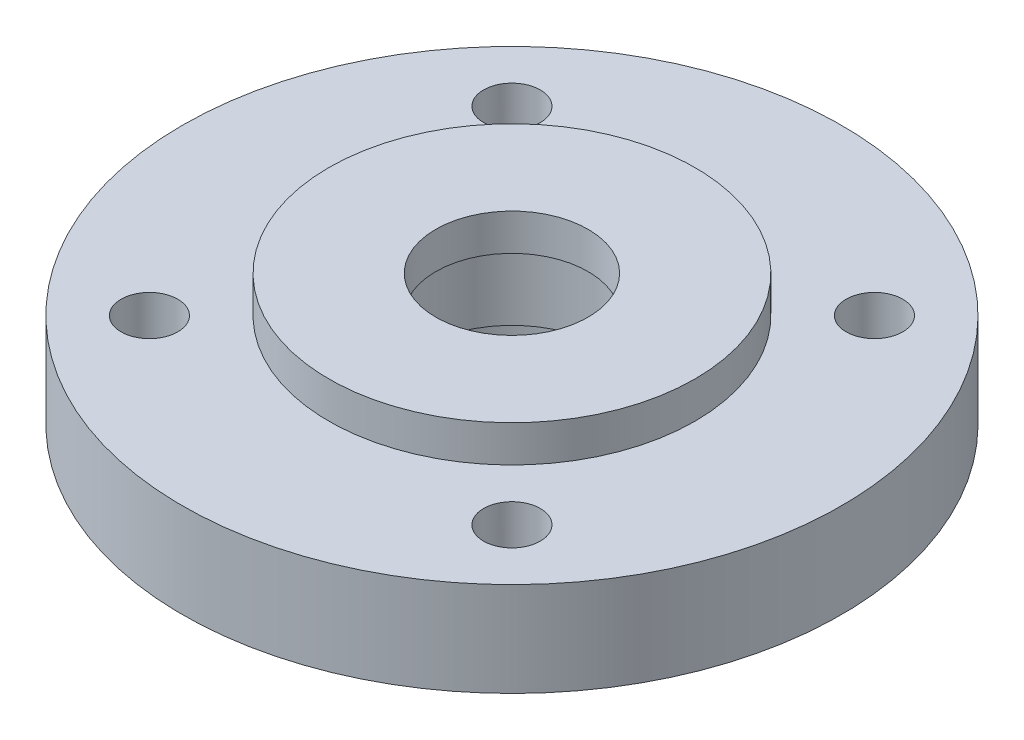
SolidWorks part; units mm, degrees
material "6061-T6 (SS)"
ref_plane "Front Plane" through (0, 0, 0) normal (0, 0, 1) x (1, 0, 0)
ref_plane "Top Plane" through (0, 0, 0) normal (0, 1, 0) x (1, 0, 0)
ref_plane "Right Plane" through (0, 0, 0) normal (1, 0, 0) x (0, 0, -1)
sketch "Sketch1" plane through (0, 0, 0) normal (0, 0, 1) x (1, 0, 0)
  line L0 (0, 0) -> (0, -62.4802) construction
  line L3 (-15.875, -62.4802) -> (-6.604, -62.4802)
  line L4 (-6.604, -62.4802) -> (-6.604, -65.6552)
  line L5 (-6.604, -65.6552) -> (-7.9375, -65.6552)
  line L6 (-7.9375, -65.6552) -> (-7.9375, -72.0052)
  line L7 (-15.875, -62.4802) -> (-15.875, -65.6552)
  line L8 (-15.875, -65.6552) -> (-28.575, -65.6552)
  line L9 (-28.575, -65.6552) -> (-28.575, -73.8302)
  line L10 (-7.9375, -72.0052) -> (-9.5, -72.0052)
  line L12 (73.025, -73.8302) -> (-73.025, -73.8302) construction
  line L14 (-14.1605, -73.8302) -> (-14.1605, -77.0052)
  line L15 (-14.1605, -77.0052) -> (-9.5, -77.0052)
  line L16 (-9.5, -77.0052) -> (-9.5, -72.0052)
  line L17 (-28.575, -73.8302) -> (-19.05, -73.8302)
  line L18 (-19.05, -73.8302) -> (-19.05, -70.6933)
  line L19 (-19.05, -70.6933) -> (-14.1605, -70.6933)
  line L20 (-14.1605, -70.6933) -> (-14.1605, -73.8302)
  dimension "D1" = 13.208
  dimension "D2" = 19
  dimension "D3" = 15.875
  dimension "D4" = 3.175
  dimension "D5" = 3.175
  dimension "D6" = 12.7
  dimension "D7" = 57.15
  dimension "D8" = 6.35
  dimension "D9" = 28.321
  dimension "D10" = 5
  dimension "D11" = 3.175
  dimension "D12" = 38.1
  dimension "D13" = 3.1369
revolve "Revolve1" add sketch "Sketch1" angle 360 about L0
hole_wizard "#10 (0.1935) Diameter Hole1" positions "Sketch2" profile "Sketch3" hole size "#10" standard "ANSI Inch" end condition through all
sketch "Sketch2" plane through (0, -62.4802, 0) normal (0, 1, 0) x (1, 0, 0)
  line L0 (-15.7154, 15.7154) -> (15.7154, -15.7154) construction
  line L2 (15.7154, 15.7154) -> (-15.7154, -15.7154) construction
  line L3 (0, 0) -> (-24.7223, 0) construction
  point P0 (15.7154, 15.7154)
  point P2 (-15.7154, 15.7154)
  point P4 (-15.7154, -15.7154)
  point P6 (15.7154, -15.7154)
  dimension "D1" = 44.45
  dimension "D2" = 45
sketch "Sketch3" plane through (15.7154, -62.4802, -15.7154) normal (1, 0, 0) x (0, 0, 1)
  line L0 (0, 0) -> (0, 14.525)
  line L1 (0, 14.525) -> (2.4574, 14.525)
  line L2 (2.4574, 14.525) -> (2.4574, 0)
  line L5 (2.4574, 0) -> (0, 0)
  line L11 (0, -6.35) -> (0, 107.95) construction
  dimension "Thru Hole Dia." = 4.9149
  dimension "Thru Hole Depth" = 14.525
